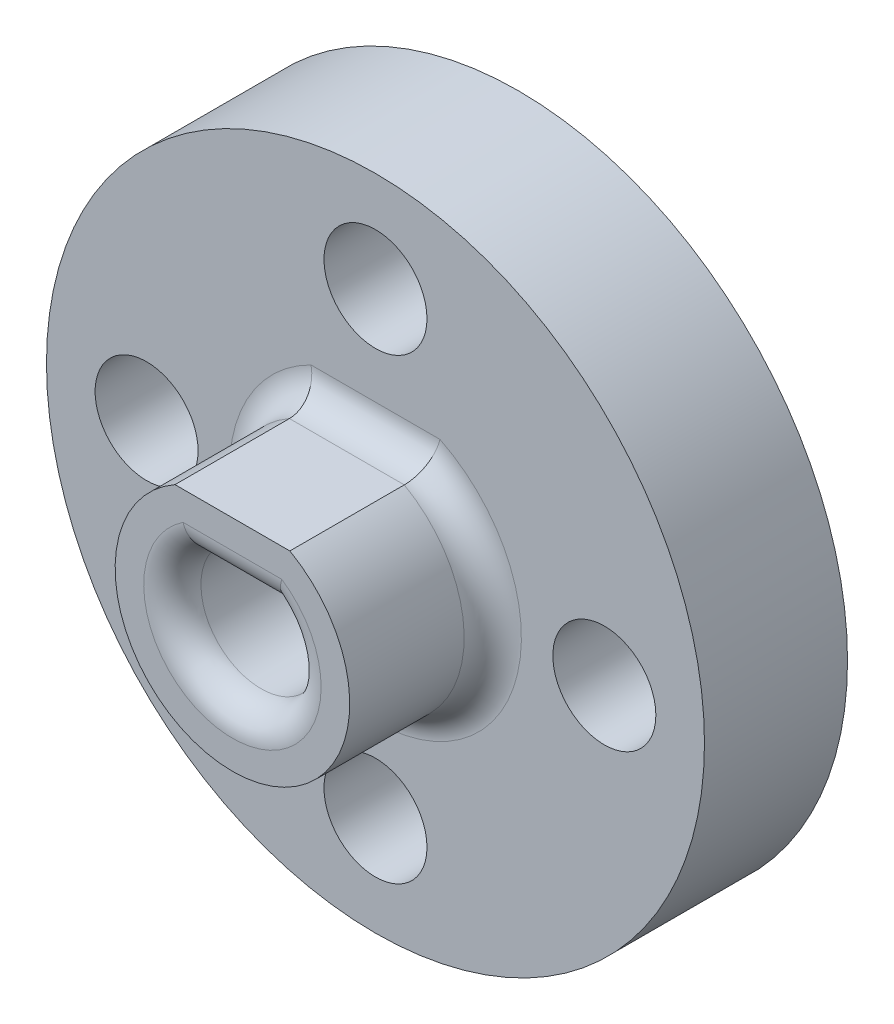
SolidWorks part; units mm, degrees
ref_plane "Front Plane" through (0, 0, 0) normal (0, 0, 1) x (1, 0, 0)
ref_plane "Top Plane" through (0, 0, 0) normal (0, 1, 0) x (1, 0, 0)
ref_plane "Right Plane" through (0, 0, 0) normal (1, 0, 0) x (0, 0, -1)
sketch "Sketch1" plane through (0, 0, 0) normal (0, 0, 1) x (1, 0, 0)
  line L0 (1.389, 1.575) -> (-1.389, 1.575)
  circle A0 centre (0, 8) radius 1.8
  circle A1 centre (8, 0) radius 1.8
  circle A2 centre (0, -8) radius 1.8
  circle A3 centre (-8, 0) radius 1.8
  circle A4 centre (0, 0) radius 11.5
  arc A5 (1.389, 1.575) -> (-1.389, 1.575) centre (0, 0) cw
  point P0 (0, 0)
  point P13 (0, 0)
  point P17 (0, -2.1)
  point P18 (-0.1604, 0)
  dimension "D1" = 3.6
  dimension "D4" = 23
  dimension "D5" = 2.1
  dimension "D2" = 8
  dimension "D6" = 3.675
  dimension "D3" = 4
extrude "Boss-Extrude1" add sketch "Sketch1" along normal blind 5 contours A4 A0 A1 A2 A3 L0 A5 region at (-11.1747, 0, 0)
extrude "Extrude-Thin1" add sketch "Sketch1<4>" along normal blind 5 from surface thin contours L0 A5 starting at face at (1.8, 8, 5) thin type one direction wall 2
sketch "Sketch1<4>" plane through (0, 0, 0) normal (0, 0, 1) x (1, 0, 0) same geometry as "Sketch1"
fillet "Fillet1" radius 1 2 edges at (0, -4.1, 5) (0, 3.575, 5)
fillet "Fillet2" radius 1 2 edges at (0, 1.575, 10) (0, -2.1, 10)
